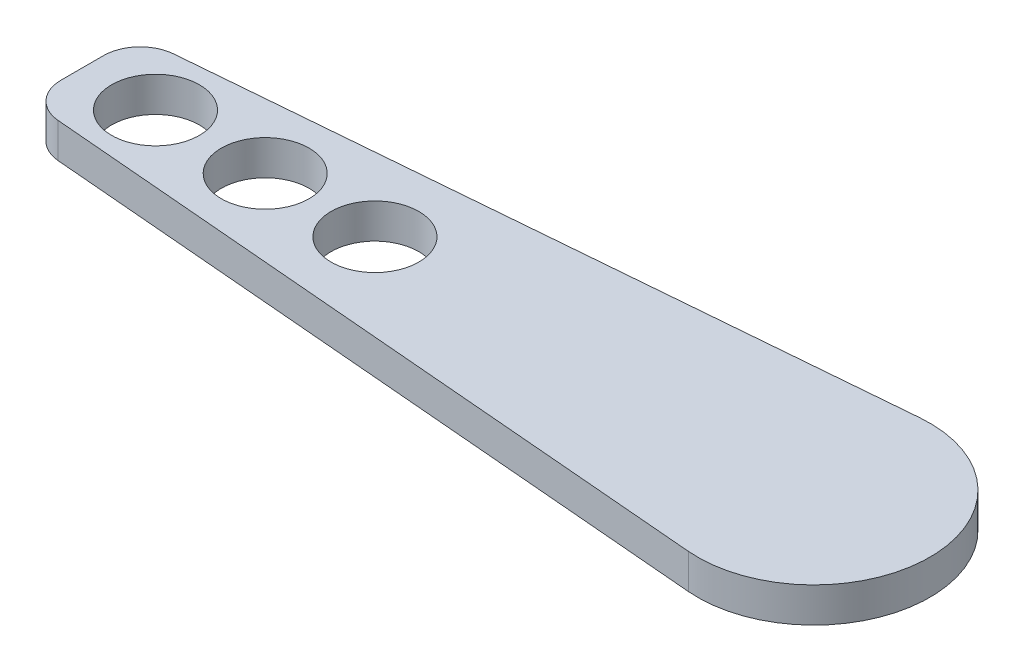
SolidWorks part; units mm, degrees
ref_plane "Front Plane" through (0, 0, 0) normal (0, 0, 1) x (1, 0, 0)
ref_plane "Top Plane" through (0, 0, 0) normal (0, 1, 0) x (1, 0, 0)
ref_plane "Right Plane" through (0, 0, 0) normal (1, 0, 0) x (0, 0, -1)
sketch "Sketch2" plane through (0, 0, 0) normal (0, 1, 0) x (1, 0, 0)
  line L0 (0, 15.9313) -> (-100, 7.5)
  line L1 (-100, -7.5) -> (-100, 7.5)
  line L2 (-100, -7.5) -> (0, -15.9313)
  line L3 (-100, 0) -> (0, 0) construction
  line L4 (-90, 0) -> (-75, 0) construction
  line L5 (-75, 0) -> (-60, 0) construction
  circle A0 centre (0, 0) radius 15.875
  circle A1 centre (-90, 0) radius 6
  circle A2 centre (-75, 0) radius 6
  circle A3 centre (-60, 0) radius 6
  point P8 (-100, 0)
  dimension "D1" = 31.75
  dimension "D3" = 12
  dimension "D2" = 100
  dimension "D4" = 15
  dimension "D5" = 10
  dimension "D6" = 15
extrude "Boss-Extrude1" add sketch "Sketch2" along normal blind 4.7625 contours A0 L0 L1 L2 A3 A2 A1 | A0 region at (-46.638, 0, 0) region at (0, 0, 0)
fillet "Fillet1" radius 5 2 edges at (-100, 2.3813, -7.5) (-100, 2.3813, 7.5)
equation "\"steeringarmlength\"=100"
equation "\"D2@Sketch2\"=\"steeringarmlength\""
equation "\"mountingholespacing\"=15"
equation "\"D4@Sketch2\"=\"mountingholespacing\""
